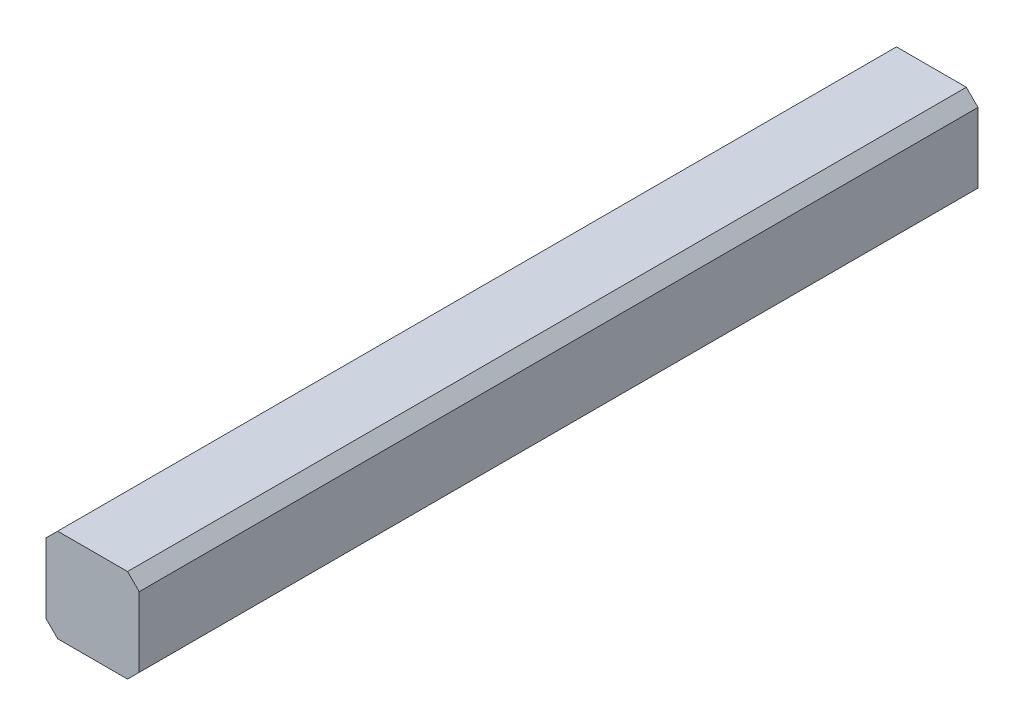
SolidWorks part; units mm, degrees
ref_plane "Front" through (0, 0, 0) normal (0, 0, 1) x (1, 0, 0)
ref_plane "Top" through (0, 0, 0) normal (0, 1, 0) x (1, 0, 0)
ref_plane "Right" through (0, 0, 0) normal (1, 0, 0) x (0, 0, -1)
sketch "body" plane through (0, 0, 0) normal (0, 0, 1) x (1, 0, 0)
  line L1 (0, 0) -> (2, 0)
  line L2 (0, 0) -> (0, 2)
  line L3 (0, 2) -> (2, 2)
  line L4 (2, 0) -> (2, 2)
  dimension "Width" = 2
  dimension "Thickness" = 2
extrude "Extrude1" add sketch "body" along normal blind 18
chamfer "Chamfer1" distance 0.25 4 edges at (0, 0, 9) (2, 0, 9) (2, 2, 9) (0, 2, 9)
